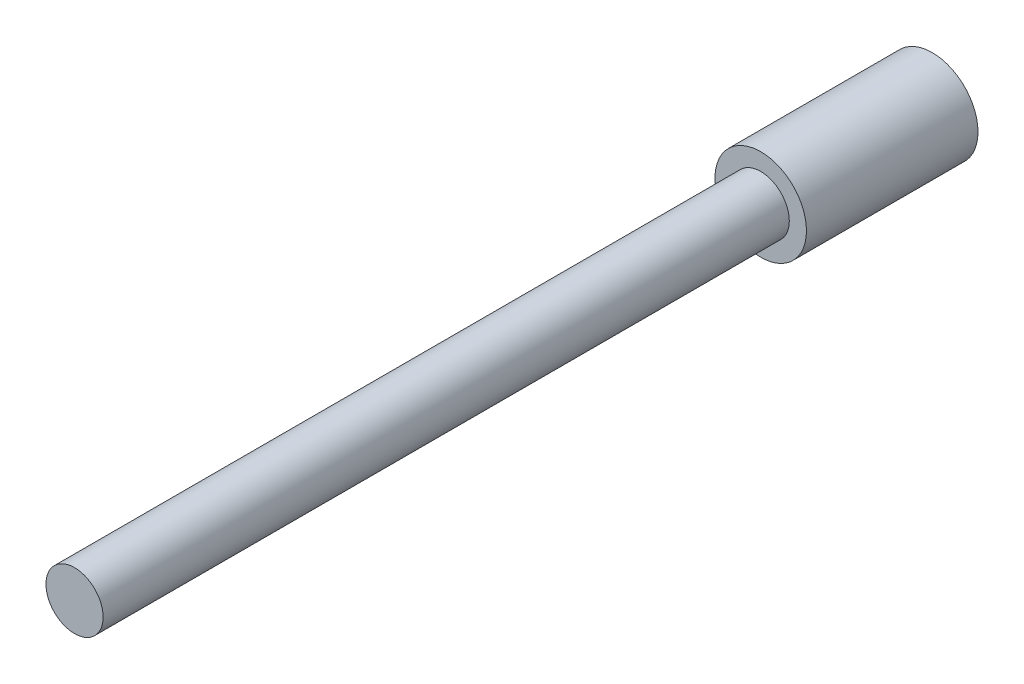
SolidWorks part; units mm, degrees
ref_plane "Front Plane" through (0, 0, 0) normal (0, 0, 1) x (1, 0, 0)
ref_plane "Top Plane" through (0, 0, 0) normal (0, 1, 0) x (1, 0, 0)
ref_plane "Right Plane" through (0, 0, 0) normal (1, 0, 0) x (0, 0, -1)
sketch "Sketch1" plane through (0, 0, 0) normal (0, 0, 1) x (1, 0, 0)
  circle A0 centre (0, 0) radius 4
  circle A1 centre (0, 0) radius 1.5
  dimension "D1" = 8
  dimension "D2" = 3
extrude "Boss-Extrude1" add sketch "Sketch1" along normal blind 15
sketch "Sketch2" plane through (0, 0, 15) normal (0, 0, 1) x (1, 0, 0)
  circle A0 centre (0, 0) radius 1.5
extrude "Boss-Extrude2" add sketch "Sketch2" against normal blind 5
sketch "Sketch3" plane through (0, 0, 15) normal (0, 0, 1) x (1, 0, 0)
  circle A0 centre (0, 0) radius 2.5
  dimension "D1" = 5
extrude "Boss-Extrude3" add sketch "Sketch3" along normal blind 60
ref_axis "Axis1" through (0, 0, 75) along (0, 0, -1)
